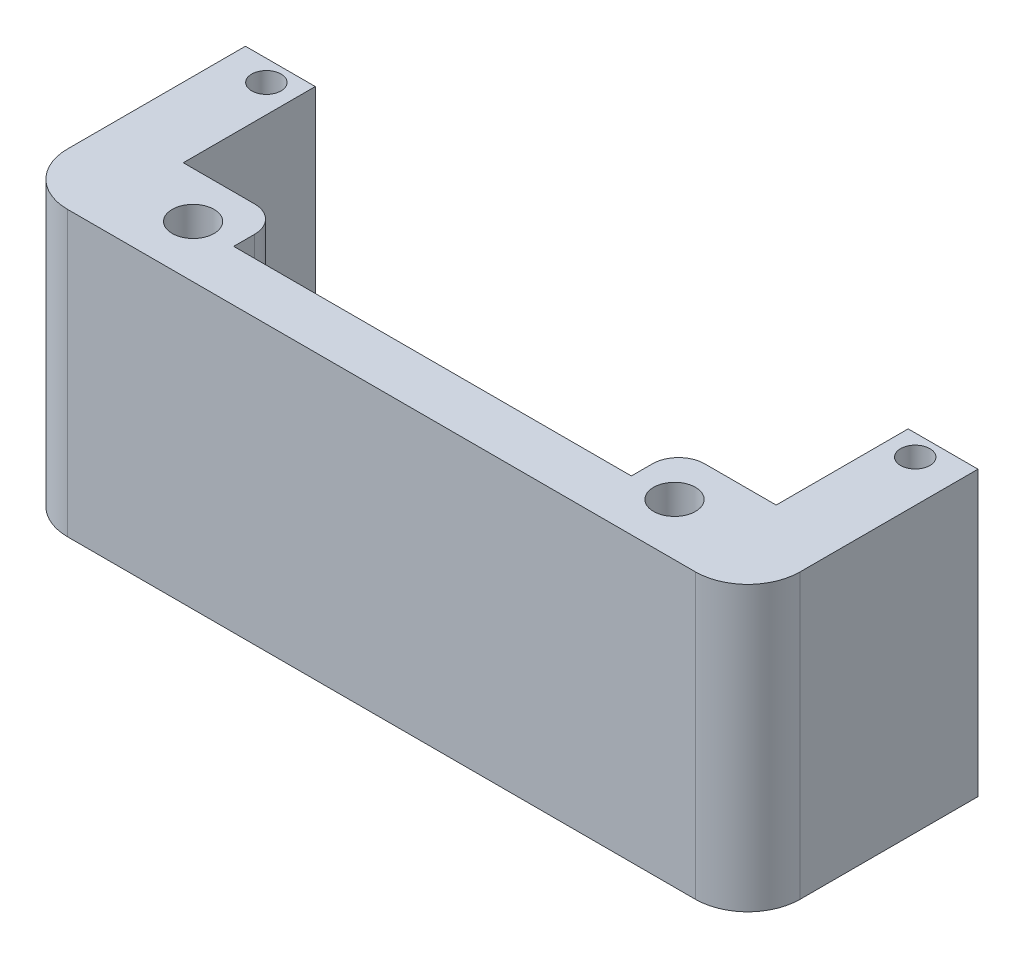
SolidWorks part; units mm, degrees
ref_plane "Front Plane" through (0, 0, 0) normal (0, 0, 1) x (1, 0, 0)
ref_plane "Top Plane" through (0, 0, 0) normal (0, 1, 0) x (1, 0, 0)
ref_plane "Right Plane" through (0, 0, 0) normal (1, 0, 0) x (0, 0, -1)
sketch "Sketch1" plane through (0, 0, 0) normal (0, 1, 0) x (1, 0, 0)
  line L0 (0, -64.962) -> (0, 64.962)
  line L1 (-38, -6.3014) -> (38, -6.3014)
  line L2 (38, -6.3014) -> (38, 27.9486)
  line L3 (-38, -6.3014) -> (-38, 27.9486)
  line L4 (38, 27.9486) -> (70, 27.9486)
  line L5 (-38, 27.9486) -> (-70, 27.9486)
  line L6 (70, 27.9486) -> (70, -16.0514)
  line L7 (-70, 27.9486) -> (-70, -16.0514)
  line L8 (70, -16.0514) -> (-70, -16.0514)
  line L9 (-70, 27.9486) -> (-37.0457, 27.9486)
  spline S0 degree 2 poles (38, -6.3014) (37.4717, -6.3148) (36.9264, -6.3014) knots 0.972384 0.972384 0.972384 1 1 1
  point P4 (0, 0)
  point P8 (0, -6.3014)
  point P15 (0, -16.0514)
  dimension "D1" = 140
  dimension "D2" = 44
  dimension "D3" = 32
  dimension "D4" = 34.25
extrude "Boss-Extrude1" add sketch "Sketch1" along normal blind 54.2 contours L8 L0 L1 L3 L5 L7 | L8 L6 L4 L2 L1 L0 region at (-46.7087, 0, -2.3811) region at (46.7088, 0, -2.3811)
fillet "Fillet1" radius 10 2 edges at (70, 27.1, 16.0514) (-70, 27.1, 16.0514)
sketch "Sketch2" plane through (0, 54.2, 0) normal (0, 1, 0) x (1, 0, 0)
  spline S0 degree 3 poles (62, 25.9486) (58, 25.9486) (58, 21.9486) (62, 21.9486) (66, 21.9486) (66, 25.9486) (62, 25.9486) (58, 25.9486) (58, 21.9486) knots -0.5 0 0 0 0.5 0.5 0.5 1 1 1 1.5 1.5 1.5 weights 1 0.333333 0.333333 1 0.333333 0.333333 1 0.333333 0.333333 only from (62, 25.9486) to (62, 25.9486) construction
  spline S2 degree 3 poles (45.9972, -10.0514) (53.9972, -10.057) (54.0028, -2.057) (46.0028, -2.0514) (38.0028, -2.0458) (37.9972, -10.0458) (45.9972, -10.0514) (53.9972, -10.057) (54.0028, -2.057) knots -0.5 0 0 0 0.5 0.5 0.5 1 1 1 1.5 1.5 1.5 weights 1 0.333333 0.333333 1 0.333333 0.333333 1 0.333333 0.333333 only from (45.9972, -10.0514) to (45.9972, -10.0514) construction
  spline S3 degree 3 poles (-50, -6.0486) (-50.0056, -14.0486) (-42.0056, -14.0542) (-42, -6.0542) (-41.9944, 1.9458) (-49.9944, 1.9514) (-50, -6.0486) (-50.0056, -14.0486) (-42.0056, -14.0542) knots -0.5 0 0 0 0.5 0.5 0.5 1 1 1 1.5 1.5 1.5 weights 1 0.333333 0.333333 1 0.333333 0.333333 1 0.333333 0.333333 only from (-50, -6.0486) to (-50, -6.0486) construction
  spline S5 degree 3 poles (-62, 21.9486) (-58, 21.9486) (-58, 25.9486) (-62, 25.9486) (-66, 25.9486) (-66, 21.9486) (-62, 21.9486) (-58, 21.9486) (-58, 25.9486) knots -0.5 0 0 0 0.5 0.5 0.5 1 1 1 1.5 1.5 1.5 weights 1 0.333333 0.333333 1 0.333333 0.333333 1 0.333333 0.333333 only from (-62, 21.9486) to (-62, 21.9486) construction
  spline S6 degree 3 poles (62, 25.9486) (58, 25.9486) (58, 21.9486) (62, 21.9486) (66, 21.9486) (66, 25.9486) (62, 25.9486) (58, 25.9486) (58, 21.9486) knots -0.5 0 0 0 0.5 0.5 0.5 1 1 1 1.5 1.5 1.5 weights 1 0.333333 0.333333 1 0.333333 0.333333 1 0.333333 0.333333 only from (62, 25.9486) to (62, 25.9486)
  spline S8 degree 3 poles (45.9972, -10.0514) (53.9972, -10.057) (54.0028, -2.057) (46.0028, -2.0514) (38.0028, -2.0458) (37.9972, -10.0458) (45.9972, -10.0514) (53.9972, -10.057) (54.0028, -2.057) knots -0.5 0 0 0 0.5 0.5 0.5 1 1 1 1.5 1.5 1.5 weights 1 0.333333 0.333333 1 0.333333 0.333333 1 0.333333 0.333333 only from (45.9972, -10.0514) to (45.9972, -10.0514)
  spline S9 degree 3 poles (-50, -6.0486) (-50.0056, -14.0486) (-42.0056, -14.0542) (-42, -6.0542) (-41.9944, 1.9458) (-49.9944, 1.9514) (-50, -6.0486) (-50.0056, -14.0486) (-42.0056, -14.0542) knots -0.5 0 0 0 0.5 0.5 0.5 1 1 1 1.5 1.5 1.5 weights 1 0.333333 0.333333 1 0.333333 0.333333 1 0.333333 0.333333 only from (-50, -6.0486) to (-50, -6.0486)
  spline S11 degree 3 poles (-62, 21.9486) (-58, 21.9486) (-58, 25.9486) (-62, 25.9486) (-66, 25.9486) (-66, 21.9486) (-62, 21.9486) (-58, 21.9486) (-58, 25.9486) knots -0.5 0 0 0 0.5 0.5 0.5 1 1 1 1.5 1.5 1.5 weights 1 0.333333 0.333333 1 0.333333 0.333333 1 0.333333 0.333333 only from (-62, 21.9486) to (-62, 21.9486)
extrude "Cut-Extrude1" cut sketch "Sketch2" against normal blind 54.2
sketch "Sketch4" plane through (0, 54.2, 0) normal (0, 1, 0) x (1, 0, 0)
  line L0 (0, -16.0514) -> (0, 33.2153) construction
  line L1 (60, -16.0514) -> (-60, -16.0514) construction
  line L2 (38, 2.7226) -> (56.6546, 2.7226)
  line L3 (38, -6.3014) -> (38, 27.9486) construction
  line L4 (-38, 2.7226) -> (-56.6546, 2.7226)
  line L5 (56.6546, 2.7226) -> (56.6546, 27.9486)
  line L6 (38, 27.9486) -> (70, 27.9486) construction
  line L7 (-56.6546, 2.7226) -> (-56.6546, 27.9486)
  line L8 (56.6546, 27.9486) -> (38, 27.9486)
  line L9 (-56.6546, 27.9486) -> (-38, 27.9486)
  line L10 (38, 27.9486) -> (38, 2.7226)
  line L11 (-38, 27.9486) -> (-38, 2.7226)
  line M9 (-38, 27.9486) -> (-70, 27.9486)
  line M17 (70, 27.9486) -> (38, 27.9486)
  line M18 (38, 27.9486) -> (38, -6.3014)
  line M21 (-38, -6.3014) -> (-38, 27.9486)
extrude "Cut-Extrude2" cut sketch "Sketch4" against normal blind 54.2 contours L7 L4 M21 M9 | L2 L5 M17 M18 | L10 L2 L5 L8 region at (47.3273, 54.2, -15.3356) region at (-47.3273, 54.2, -15.3356)
fillet "Fillet3" radius 5 2 edges at (38, 27.1, -2.7226) (-38, 27.1, -2.7226)
sketch "Sketch5" plane through (0, 54.2, 0) normal (0, 1, 0) x (1, 0, 0)
  circle A0 centre (-62, 23.9486) radius 2.8
  circle A1 centre (62, 23.9486) radius 2.8
  dimension "D1" = 5.6
  dimension "D2" = 5.6
extrude "Cut-Extrude3" cut sketch "Sketch5" against normal through all
